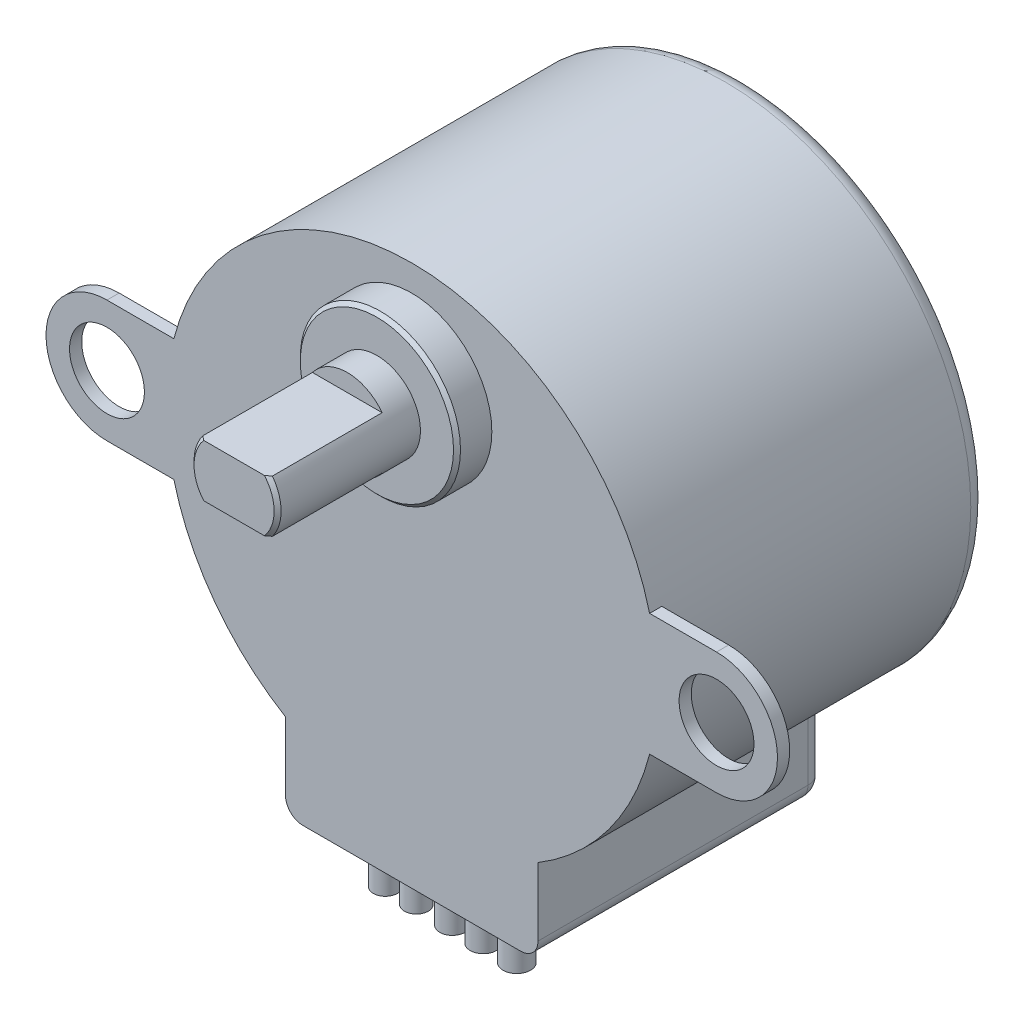
SolidWorks part; units mm, degrees
material "Q235-A"
ref_plane "前视" through (0, 0, 0) normal (0, 0, 1) x (1, 0, 0)
ref_plane "上视" through (0, 0, 0) normal (0, 1, 0) x (1, 0, 0)
ref_plane "右视" through (0, 0, 0) normal (1, 0, 0) x (0, 0, -1)
sketch "草图1" plane through (0, 0, 0) normal (0, 0, 1) x (1, 0, 0)
  line L0 (0, 0) -> (0, -27.8833) construction
  circle A0 centre (0, 0) radius 14.1
  dimension "D1" = 28.2
extrude "凸台-拉伸1" add sketch "草图1" along normal blind 19
sketch "草图2" plane through (0, 0, 19) normal (0, 0, 1) x (1, 0, 0)
  line L0 (0, 0) -> (0, 14.7645) construction
  line L1 (-21.5247, 0) -> (21.5247, 0) construction
  line L2 (-17.5, 0) -> (17.5, 0) construction
  line L3 (-17.5, 3.5) -> (17.5, 3.5)
  line L4 (-17.5, -3.5) -> (17.5, -3.5)
  arc A0 (-17.5, 3.5) -> (-17.5, -3.5) centre (-17.5, 0) ccw
  arc A1 (17.5, -3.5) -> (17.5, 3.5) centre (17.5, 0) ccw
  circle A2 centre (-17.5, 0) radius 2.15
  circle A3 centre (17.5, 0) radius 2.15
  point P7 (0, 0)
  dimension "D2" = 35
  dimension "D3" = 4.3
  dimension "D1" = 7
extrude "凸台-拉伸2" add sketch "草图2" against normal blind 0.7
fillet "圆角1" radius 1 1 edges at (14.1, 0, 0)
sketch "草图3" plane through (0, 0, 19) normal (0, 0, 1) x (1, 0, 0)
  line L0 (0, 0) -> (0, 15.6713) construction
  circle A0 centre (0, 8) radius 4.6
  dimension "D1" = 8
  dimension "D2" = 9.2
extrude "凸台-拉伸3" add sketch "草图3" along normal blind 2
sketch "草图4" plane through (0, 0, 21) normal (0, 0, 1) x (1, 0, 0)
  circle A0 centre (0, 8) radius 2.5
  dimension "D1" = 5
extrude "凸台-拉伸4" add sketch "草图4" along normal blind 8.2
sketch "草图5" plane through (0, 0, 29.2) normal (0, 0, 1) x (1, 0, 0)
  line L0 (-6.2974, 8) -> (5.9609, 8) construction
  line L1 (-2, 9.5) -> (2, 9.5)
  line L2 (-2, 6.5) -> (2, 6.5)
  circle A0 centre (0, 8) radius 2.5 construction
  arc A1 (-2, 6.5) -> (2, 6.5) centre (0, 8) ccw
  circle A2 centre (0, 8) radius 2.5 construction
  arc A3 (2, 9.5) -> (-2, 9.5) centre (0, 8) ccw
  dimension "D1" = 3
extrude "切除-拉伸1" cut sketch "草图5" against normal blind 6.5
chamfer "倒角1" distance 0.2 angle 45 3 edges at (2.5, 8, 29.2) (-2.5, 8, 29.2) (4.6, 8, 21)
sketch "草图6" plane through (0, 0, 19) normal (0, 0, 1) x (1, 0, 0)
  line L0 (0, 0) -> (0, -24.7541) construction
  line L3 (-7.25, -12.0933) -> (-7.25, -17)
  line L4 (-7.25, -17) -> (7.25, -17)
  line L5 (7.25, -12.0933) -> (7.25, -17)
  arc A0 (-13.6587, -3.5) -> (13.6587, -3.5) centre (0, 0) ccw construction
  arc A1 (-7.25, -12.0933) -> (7.25, -12.0933) centre (0, 0) ccw
  dimension "D1" = 14.5
  dimension "D2" = 17
extrude "凸台-拉伸5" add sketch "草图6" against normal blind 16.5
fillet "圆角2" radius 1 5 edges at (7.25, -17, 10.75) (7.25, -14.5466, 2.5) (0, -17, 2.5) (-7.25, -17, 10.75) (-7.25, -14.5466, 2.5)
sketch "草图7" plane through (0, -17, 0) normal (0, -1, 0) x (1, 0, 0)
  circle A0 centre (-3.8457, 16.6671) radius 0.6933
  circle A1 centre (-2.0671, 16.6671) radius 0.6832
  circle A2 centre (0, 16.6671) radius 0.7211
  circle A3 centre (1.7786, 16.6671) radius 0.7524
  circle A4 centre (3.7015, 16.6671) radius 0.7884
extrude "凸台-拉伸6" add sketch "草图7" along normal blind 3
